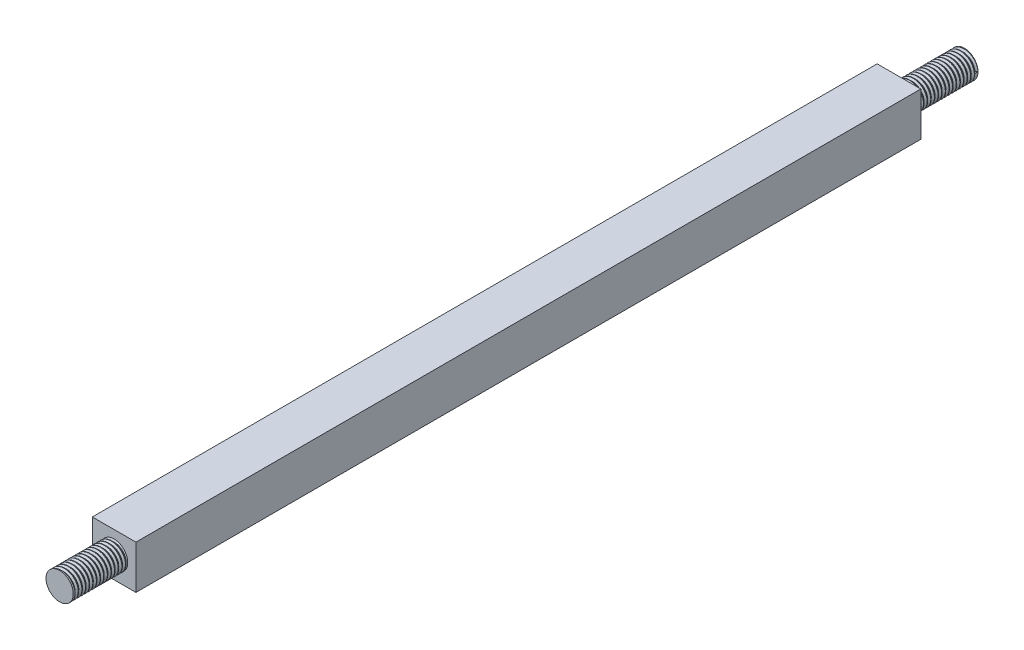
SolidWorks part; units mm, degrees
ref_plane "Front Plane" through (0, 0, 0) normal (0, 0, 1) x (1, 0, 0)
ref_plane "Top Plane" through (0, 0, 0) normal (0, 1, 0) x (1, 0, 0)
ref_plane "Right Plane" through (0, 0, 0) normal (1, 0, 0) x (0, 0, -1)
sketch "Sketch1" plane through (0, 0, 0) normal (0, 0, 1) x (1, 0, 0)
  line L1 (-6.35, -6.35) -> (6.35, -6.35)
  line L2 (-6.35, -6.35) -> (-6.35, 6.35)
  line L3 (-6.35, 6.35) -> (6.35, 6.35)
  line L4 (6.35, -6.35) -> (6.35, 6.35)
  line L5 (-6.35, -6.35) -> (6.35, 6.35) construction
  line L6 (-6.35, 6.35) -> (6.35, -6.35) construction
  point P0 (0, 0)
extrude "Boss-Extrude1" add sketch "Sketch1" along normal blind 228.6
sketch "Sketch2" plane through (0, 0, 228.6) normal (0, 0, 1) x (1, 0, 0)
  circle A0 centre (0, 0) radius 3.9688
extrude "Boss-Extrude2" add sketch "Sketch2" along normal blind 15.875
thread "Thread1" pitch 1.0583 method cut profile "Thread Profile1" start angle 0, offset 0, length 0, pitch 1.0583, diameter 7.9375
ref_plane "Plane1" through (-3.9688, 0, 244.475) normal (0, -1, 0) x (-1, 0, 0)
sketch "Thread Profile1" plane through (-3.9688, 0, 244.475) normal (0, -1, 0) x (-1, 0, 0)
  line L0 (0, 0) -> (0, 1.0583) construction
  line L11 (0, 0) -> (0, 0.926)
  line L12 (0, 0.926) -> (-0.5728, 0.5953)
  line L13 (-0.5728, 0.5953) -> (-0.5728, 0.3307)
  line L15 (-0.5728, 0.3307) -> (0, 0)
  line L17 (-0.5728, 0.463) -> (0, 0.463) construction
  point P2 (0, 0)
  dimension "Pitch" = 1.0583
  dimension "Profile_Angle" = 60
  dimension "Profile_Land" = 0.2646
  dimension "Profile_Height" = 0.5728
sketch "Sketch6" plane through (0, 0, 0) normal (0, 0, -1) x (-1, 0, 0)
  circle A0 centre (0, 0) radius 3.9688
extrude "Boss-Extrude3" add sketch "Sketch6" along normal blind 19.05
thread "Thread2" pitch 1.0583 method cut profile "Thread Profile2" start angle 0, offset 0, length 0, pitch 1.0583, diameter 7.9375
ref_plane "Plane2" through (3.9688, 0, -19.05) normal (0, -1, 0) x (1, 0, 0)
sketch "Thread Profile2" plane through (3.9688, 0, -19.05) normal (0, -1, 0) x (1, 0, 0)
  line L0 (0, 0) -> (0, 1.0583) construction
  line L11 (0, 0) -> (0, 0.926)
  line L12 (0, 0.926) -> (-0.5728, 0.5953)
  line L13 (-0.5728, 0.5953) -> (-0.5728, 0.3307)
  line L15 (-0.5728, 0.3307) -> (0, 0)
  line L17 (-0.5728, 0.463) -> (0, 0.463) construction
  point P2 (0, 0)
  dimension "Pitch" = 1.0583
  dimension "Profile_Angle" = 60
  dimension "Profile_Land" = 0.2646
  dimension "Profile_Height" = 0.5728
